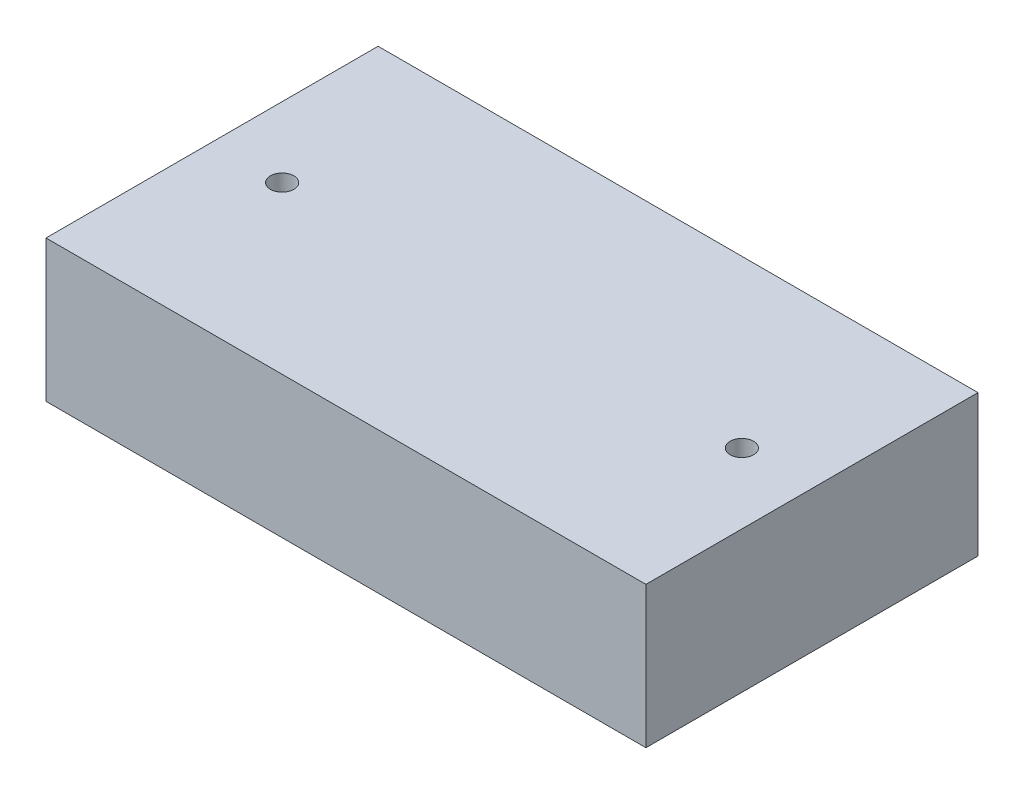
SolidWorks part; units mm, degrees
ref_plane "Спереди" through (0, 0, 0) normal (0, 0, 1) x (1, 0, 0)
ref_plane "Сверху" through (0, 0, 0) normal (0, 1, 0) x (1, 0, 0)
ref_plane "Справа" through (0, 0, 0) normal (1, 0, 0) x (0, 0, -1)
other "Configuration Table"
sketch "Эскиз1" plane through (0, 0, 0) normal (0, 1, 0) x (1, 0, 0)
  line L1 (-38.3, -21.2) -> (38.3, -21.2)
  line L2 (-38.3, -21.2) -> (-38.3, 21.2)
  line L3 (-38.3, 21.2) -> (38.3, 21.2)
  line L4 (38.3, -21.2) -> (38.3, 21.2)
  line L5 (-38.3, -21.2) -> (38.3, 21.2) construction
  line L6 (-38.3, 21.2) -> (38.3, -21.2) construction
  point P0 (0, 0)
  dimension "D1" = 76.6
  dimension "D2" = 42.4
extrude "Бобышка-Вытянуть1" add sketch "Эскиз1" along normal blind 18.07
sketch "Эскиз2" plane through (0, 18.07, 0) normal (0, 1, 0) x (1, 0, 0)
  line L0 (0, 0) -> (58.7, 0) construction
  line L1 (0, 0) -> (0, 38.349) construction
  line L2 (38.3, -21.2) -> (38.3, 21.2) construction
  circle A0 centre (29.35, 0) radius 1.5
  circle A1 centre (-29.35, 0) radius 1.5
  point P6 (30.85, 0)
  dimension "D2" = 3
  dimension "D1" = 7.45
extrude "Вырез-Вытянуть1" cut sketch "Эскиз2" against normal blind 10
